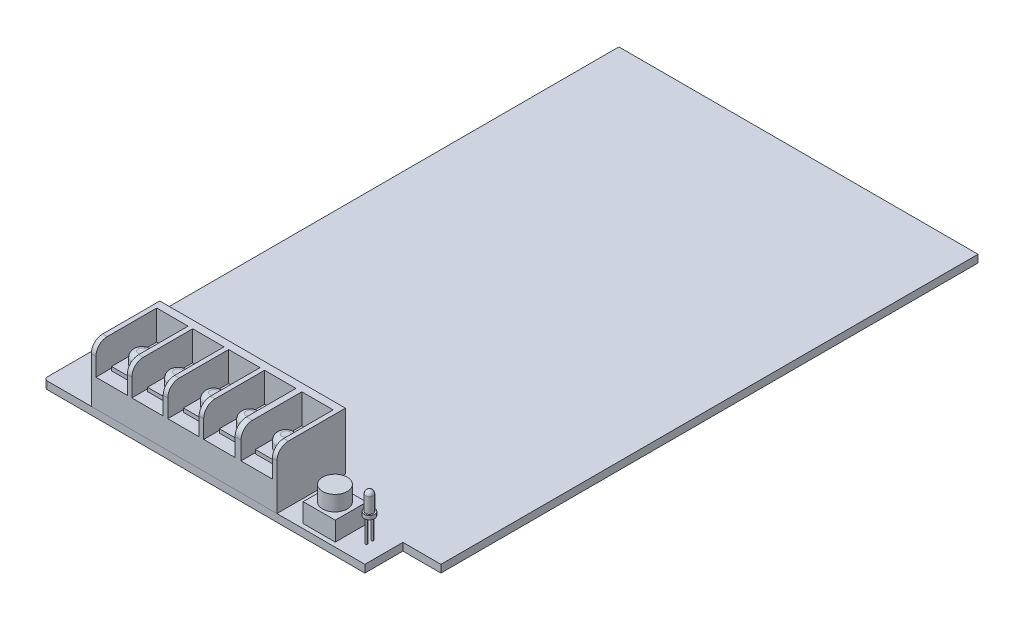
SolidWorks part; units mm, degrees
ref_plane "Front Plane" through (0, 0, 0) normal (0, 0, 1) x (1, 0, 0)
ref_plane "Top Plane" through (0, 0, 0) normal (0, 1, 0) x (1, 0, 0)
ref_plane "Right Plane" through (0, 0, 0) normal (1, 0, 0) x (0, 0, -1)
sketch "Sketch1" plane through (0, 0, 0) normal (0, 1, 0) x (1, 0, 0)
  line L1 (-47.21, -75.6) -> (47.21, -75.6)
  line L2 (-47.21, -75.6) -> (-47.21, 75.6)
  line L3 (-47.21, 75.6) -> (47.21, 75.6)
  line L4 (47.21, -75.6) -> (47.21, 75.6)
  line L5 (-47.21, -75.6) -> (47.21, 75.6) construction
  line L6 (-47.21, 75.6) -> (47.21, -75.6) construction
  point P0 (0, 0)
  dimension "D1" = 94.42
  dimension "D2" = 151.2
extrude "Extrude1" add sketch "Sketch1" along normal blind 2
fillet "Fillet1" radius 1 1 edges at (-47.21, 1, 75.6)
sketch "Sketch2" plane through (0, 2, 0) normal (0, 1, 0) x (1, 0, 0)
  line L0 (-46.21, -75.6) -> (47.21, -75.6) construction
  line L1 (-34.71, -75.6) -> (14.09, -75.6)
  line L2 (-34.71, -75.6) -> (-34.71, -57.6)
  line L3 (-34.71, -57.6) -> (14.09, -57.6)
  line L4 (14.09, -75.6) -> (14.09, -57.6)
  line L5 (-47.21, 75.6) -> (-47.21, -74.6) construction
  dimension "D1" = 48.8
  dimension "D2" = 12.5
  dimension "D3" = 18
extrude "Extrude2" add sketch "Sketch2" along normal blind 15 separate body
sketch "Sketch3" plane through (0, 0, 75.6) normal (0, 0, 1) x (1, 0, 0)
  line L0 (-34.71, 17) -> (14.09, 17) construction
  line L1 (-33.51, 17) -> (-25.26, 17)
  line L2 (-33.51, 17) -> (-33.51, 9.25)
  line L3 (-33.51, 9.25) -> (-25.26, 9.25)
  line L4 (-25.26, 17) -> (-25.26, 9.25)
  line L5 (-34.71, 17) -> (-34.71, 2) construction
  line L6 (-24.06, 17) -> (-15.81, 17)
  line L7 (-24.06, 17) -> (-24.06, 9.25)
  line L8 (-24.06, 9.25) -> (-15.81, 9.25)
  line L9 (-15.81, 17) -> (-15.81, 9.25)
  line L10 (-14.61, 17) -> (-6.36, 17)
  line L11 (-14.61, 17) -> (-14.61, 9.25)
  line L12 (-14.61, 9.25) -> (-6.36, 9.25)
  line L13 (-6.36, 17) -> (-6.36, 9.25)
  line L14 (-5.16, 17) -> (3.09, 17)
  line L15 (-5.16, 17) -> (-5.16, 9.25)
  line L16 (-5.16, 9.25) -> (3.09, 9.25)
  line L17 (3.09, 17) -> (3.09, 9.25)
  line L18 (4.64, 17) -> (12.89, 17)
  line L19 (4.64, 17) -> (4.64, 9.25)
  line L20 (4.64, 9.25) -> (12.89, 9.25)
  line L21 (12.89, 17) -> (12.89, 9.25)
  line L22 (14.09, 17) -> (14.09, 2) construction
  line L23 (-34.71, 2) -> (14.09, 2) construction
  dimension "D1" = 1.2
  dimension "D2" = 1.2
  dimension "D3" = 8.25
  dimension "D4" = 1.2
  dimension "D5" = 8.25
  dimension "D6" = 1.2
  dimension "D7" = 8.25
  dimension "D8" = 1.2
  dimension "D9" = 8.25
  dimension "D10" = 8.25
  dimension "D11" = 7.25
extrude "Extrude3" cut sketch "Sketch3" against normal blind 16
fillet "Fillet2" radius 3 6 edges at (13.49, 17, 75.6) (3.865, 17, 75.6) (-5.76, 17, 75.6) (-15.21, 17, 75.6) (-24.66, 17, 75.6) (-34.11, 17, 75.6)
sketch "Sketch4" plane through (0, 9.25, 0) normal (0, 1, 0) x (1, 0, 0)
  line L0 (-33.51, -59.6) -> (-25.26, -75.6) construction
  line L1 (-32.885, -72.1) -> (-25.885, -72.1)
  line L2 (-32.885, -72.1) -> (-32.885, -63.1)
  line L3 (-32.885, -63.1) -> (-25.885, -63.1)
  line L4 (-25.885, -72.1) -> (-25.885, -63.1)
  line L5 (-32.885, -72.1) -> (-25.885, -63.1) construction
  line L6 (-32.885, -63.1) -> (-25.885, -72.1) construction
  point P0 (-29.385, -67.6)
  dimension "D1" = 7
  dimension "D2" = 9
extrude "Extrude4" add sketch "Sketch4" along normal blind 1 separate body
sketch "Sketch5" plane through (0, 10.25, 0) normal (0, 1, 0) x (1, 0, 0)
  line L0 (-29.385, -63.1) -> (-29.385, -72.1) construction
  line L1 (-25.885, -63.1) -> (-32.885, -63.1) construction
  line L2 (-32.885, -72.1) -> (-25.885, -72.1) construction
  circle A0 centre (-29.385, -67.6) radius 2.5
  dimension "D1" = 5
extrude "Extrude5" add sketch "Sketch5" along normal blind 3 separate body
fillet "Fillet3" radius 1.5 1 edges at (-29.385, 13.25, 70.1)
pattern_linear "LPattern1" count 5 spacing 9.45 along (1, 0, 0) of bodies 104 105
sketch "Sketch6" plane through (0, 2, 0) normal (0, 1, 0) x (1, 0, 0)
  line L1 (19.832, -66.1894) -> (28.2677, -66.1894)
  line L2 (19.832, -66.1894) -> (19.832, -74.4365)
  line L3 (19.832, -74.4365) -> (28.2677, -74.4365)
  line L4 (28.2677, -66.1894) -> (28.2677, -74.4365)
extrude "Extrude6" add sketch "Sketch6" along normal blind 5 separate body
sketch "Sketch7" plane through (0, 7, 0) normal (0, 1, 0) x (1, 0, 0)
  line L0 (28.2677, -66.1894) -> (19.832, -74.4365) construction
  line L1 (19.832, -74.4365) -> (28.2677, -74.4365) construction
  line L2 (19.832, -66.1894) -> (19.832, -74.4365) construction
  circle A0 centre (24.0498, -70.3129) radius 3.25
  dimension "D1" = 6.5
extrude "Extrude7" add sketch "Sketch7" along normal blind 4 separate body
sketch "Sketch8" plane through (0, 2, 0) normal (0, 1, 0) x (1, 0, 0)
  line L1 (47.21, -75.6) -> (37.21, -75.6)
  line L2 (47.21, -75.6) -> (47.21, -65.6)
  line L3 (47.21, -65.6) -> (37.21, -65.6)
  line L4 (37.21, -75.6) -> (37.21, -65.6)
  dimension "D1" = 10
  dimension "D2" = 10
extrude "Cut-Extrude1" cut sketch "Sketch8" against normal through all
sketch "Sketch9" plane through (0, 2, 0) normal (0, 1, 0) x (1, 0, 0)
  circle A0 centre (32.7309, -69.1353) radius 0.25
  circle A1 centre (32.7309, -70.7123) radius 0.25
  dimension "D1" = 0.5
extrude "Extrude8" add sketch "Sketch9" along normal blind 6 separate body
sketch "Sketch10" plane through (0, 8, 0) normal (0, 1, 0) x (1, 0, 0)
  line L0 (32.7309, -69.1353) -> (32.7309, -70.7123) construction
  circle A0 centre (32.7309, -69.9238) radius 1.3689
extrude "Extrude9" add sketch "Sketch10" along normal blind 1 separate body
sketch "Sketch11" plane through (0, 9, 0) normal (0, 1, 0) x (1, 0, 0)
  circle A0 centre (32.7309, -69.9238) radius 1
  dimension "D1" = 2
extrude "Extrude10" add sketch "Sketch11" along normal blind 4
dome "Dome1" faces to dome 1 distance 1 reverse direction no elliptical dome no face at (32.7309, 13, 70.9238) parameters "D1"=1
